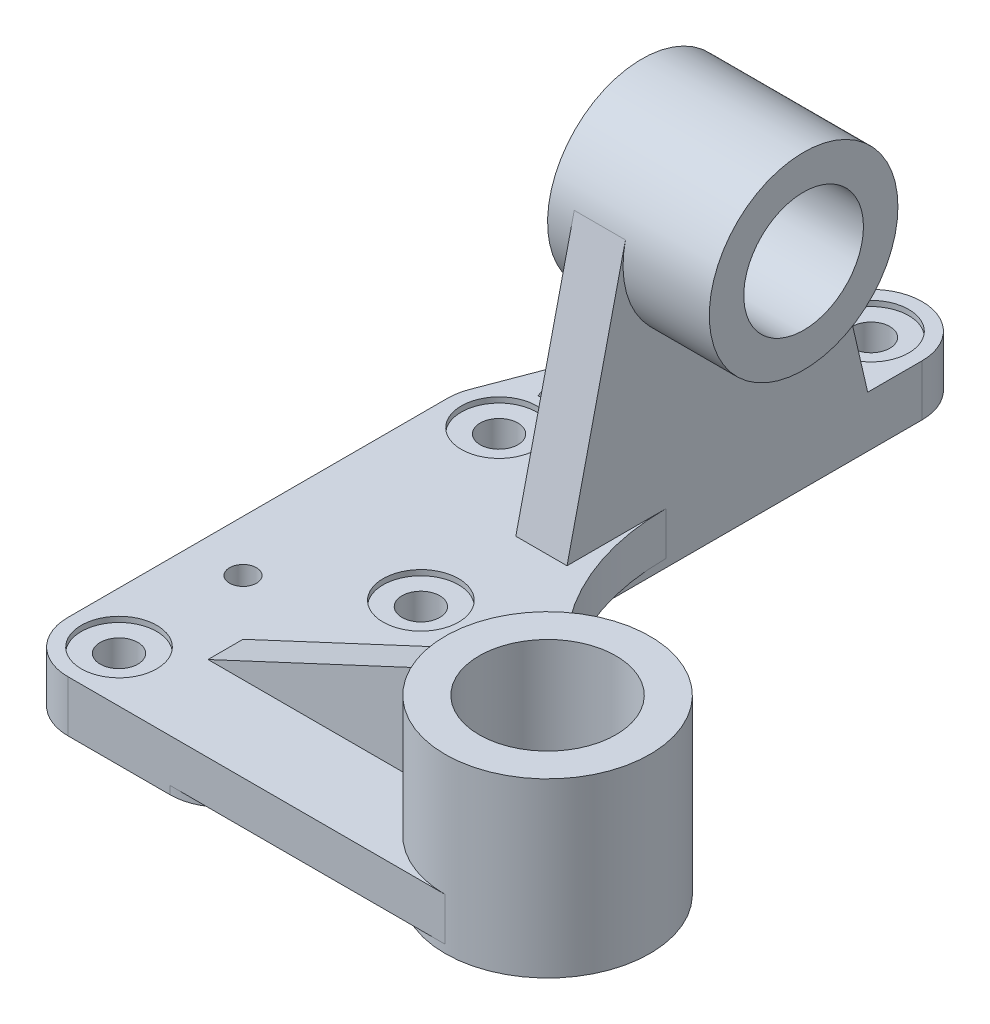
SolidWorks part; units mm, degrees
ref_plane "Front Plane" through (0, 0, 0) normal (0, 0, 1) x (1, 0, 0)
ref_plane "Top Plane" through (0, 0, 0) normal (0, 1, 0) x (1, 0, 0)
ref_plane "Right Plane" through (0, 0, 0) normal (1, 0, 0) x (0, 0, -1)
sketch "Sketch1" plane through (0, 0, 0) normal (0, 1, 0) x (1, 0, 0)
  line L0 (0, 0) -> (-27655.1875, 0) construction
  line L1 (0, 0) -> (0, -27655.1875) construction
  line L2 (0, -38) -> (-140, -38)
  line L3 (-159, -19) -> (-159, 122)
  line L4 (-157.7609, 128.7491) -> (-119.7609, 228.7491)
  line L5 (-83, 222) -> (-83, 126.8582)
  circle A0 centre (0, 0) radius 25.38
  circle A1 centre (0, 0) radius 38
  arc A3 (-159, 122) -> (-157.7609, 128.7491) centre (-140, 122) cw
  arc A4 (-140, -38) -> (-159, -19) centre (-140, -19) cw
  arc A6 (-83, 222) -> (-119.7609, 228.7491) centre (-102, 222) ccw
  arc A7 (-83, 126.8582) -> (1.7953, 37.9576) centre (6, 126.8582) ccw
  point P14 (-159, 125.4883)
  point P17 (-159, -38)
  dimension "D1" = 76
  dimension "D2" = 50.76
  dimension "D5" = 19
  dimension "D6" = 241
  dimension "D8" = 38
  dimension "D9" = 178
  dimension "D3" = 159
  dimension "D4" = 100
  dimension "D7" = 38
extrude "Boss-Extrude1" add sketch "Sketch1" along normal blind 19 contours A7 L5 A6 L4 A3 L3 A4 L2 A1 region at (-103.6495, 0, -70.7701)
extrude "Boss-Extrude2" add sketch "Sketch1<3>" along normal blind 64 contours A1 A0 region at (-36.9149, 0, -0.8725)
sketch "Sketch1<3>" plane through (0, 0, 0) normal (0, 1, 0) x (1, 0, 0) same geometry as "Sketch1"
sketch "Sketch2" plane through (-83, 0, 0) normal (1, 0, 0) x (0, 0, -1)
  line L0 (90.2247, 19) -> (201.7753, 19)
  line L1 (201.7753, 19) -> (180.103, 112.8733)
  line L2 (90.2247, 19) -> (111.897, 112.8733)
  line L3 (222, 19) -> (126.8582, 19) construction
  line L4 (-38, 64) -> (38, 64) construction
  circle A0 centre (146, 105) radius 22.205
  circle A1 centre (146, 105) radius 35
  point P13 (0, 64)
  line M8 (222, 19) -> (126.8582, 19)
  dimension "D1" = 44.41
  dimension "D2" = 70
  dimension "D3" = 77
  dimension "D4" = 77
  dimension "D5" = 146
  dimension "D6" = 41
extrude "Boss-Extrude3" add sketch "Sketch2" against normal blind 19 contours A1 L2 L0 L1 M8 region at (-83, 48.8577, -146)
extrude "Boss-Extrude4" add sketch "Sketch2<3>" along normal blind 32 and the other way blind 28 contours A1 A0 region at (-83, 139.0101, -146)
sketch "Sketch2<3>" plane through (-83, 0, 0) normal (1, 0, 0) x (0, 0, -1) same geometry as "Sketch2"
ref_plane "Plane1" through (0, 0, -146) normal (0, 0, 1) x (1, 0, 0)
sketch "Sketch3" plane through (0, 0, -146) normal (0, 0, 1) x (1, 0, 0)
  line L0 (-111, 70) -> (-143, 19)
  line L1 (-140, 19) -> (-159, 19) construction
  line L2 (-102, 19) -> (-102, 112.8733) construction
  dimension "D1" = 41
rib "Rib1" sketch "Sketch3" sketch "Sketch3" thickness 13 extrusion direction parallel to sketch draft on no parameters "D1"=13
ref_plane "Plane2" through (0, 0, 0) normal (0, 0, 1) x (1, 0, 0)
sketch "Sketch4" plane through (0, 0, 0) normal (0, 0, 1) x (1, 0, 0)
  line L0 (-38, 57) -> (-119.4913, 19)
  line L1 (-38, 64) -> (-38, 19) construction
  line L2 (-143, 19) -> (-102, 19) construction
  line L3 (0, 19) -> (-140, 19) construction
  dimension "D1" = 38
  dimension "D2" = 25
rib "Rib6" sketch "Sketch4" sketch "Sketch4" thickness 13 extrusion direction parallel to sketch draft on no parameters "D1"=13
hole_wizard "CBORE for M5 Hex Head Bolt1" positions "Sketch9" profile "Sketch10" counterbore size "M5" standard "ANSI Metric" end condition through all
sketch "Sketch9" plane through (0, 19, 0) normal (0, 1, 0) x (1, 0, 0)
  arc A0 (-157.7609, 128.7491) -> (-159, 122) centre (-140, 122) ccw construction
  arc A1 (-83, 222) -> (-119.7609, 228.7491) centre (-102, 222) ccw construction
  arc A2 (-159, -19) -> (-140, -38) centre (-140, -19) ccw construction
  point P0 (-140, -19)
  point P3 (-140, 122)
  point P6 (-102, 222)
  point P9 (-99, 52)
  dimension "D1" = 70
  dimension "D2" = 41
sketch "Sketch10" plane through (-140, 19, 19) normal (1, 0, 0) x (0, 0, 1)
  line L0 (0, 0) -> (0, 19)
  line L1 (0, 19) -> (7, 19)
  line L3 (7, 19) -> (7, 2)
  line L4 (7, 2) -> (14, 2)
  line L5 (14, 2) -> (14, 0)
  line L7 (14, 0) -> (0, 0)
  line L11 (0, -6.35) -> (0, 107.95) construction
  dimension "Thru Hole Dia." = 14
  dimension "Thru Hole Depth" = 19
  dimension "C'Bore Dia." = 28
  dimension "C'Bore Depth" = 2
hole_wizard "Ø10.0mm Dowel Hole1" positions "Sketch12" profile "Sketch13" hole size "Ø10.0" standard "ANSI Metric" end condition through all
sketch "Sketch12" plane through (0, 19, 0) normal (0, 1, 0) x (1, 0, 0)
  line L0 (-159, -19) -> (-159, 122) construction
  circle A1 centre (-99, 52) radius 7 construction
  circle A2 centre (-102, 222) radius 7 construction
  point P0 (-140, 27)
  point P2 (-115, 197)
  point P5 (0, 0)
  dimension "D2" = 25
  dimension "D3" = 13
  dimension "D4" = 25
  dimension "D1" = 19
sketch "Sketch13" plane through (-140, 19, -27) normal (1, 0, 0) x (0, 0, 1)
  line L0 (0, 0) -> (0, 19)
  line L1 (0, 19) -> (5, 19)
  line L2 (5, 19) -> (5, 0)
  line L5 (5, 0) -> (0, 0)
  line L11 (0, -6.35) -> (0, 107.95) construction
  dimension "Thru Hole Dia." = 10
  dimension "Thru Hole Depth" = 19
sketch "Sketch14" plane through (0, 0, 0) normal (0, -1, 0) x (1, 0, 0)
  line L0 (-83, -126.8582) -> (-83, 38)
  line L1 (0, 38) -> (-140, 38) construction
  line L2 (-83, 38) -> (0, 38)
  arc A0 (1.7953, -37.9576) -> (-83, -126.8582) centre (6, -126.8582) ccw construction
  arc A2 (1.7953, -37.9576) -> (-83, -126.8582) centre (6, -126.8582) ccw
  circle A4 centre (0, 0) radius 38 construction
  arc A5 (0, 38) -> (1.7953, -37.9576) centre (0, 0) ccw
extrude "Cut-Extrude1" cut sketch "Sketch14" against normal blind 3
fillet "Fillet1" radius 19 1 edges at (-83, 1.5, 38)
